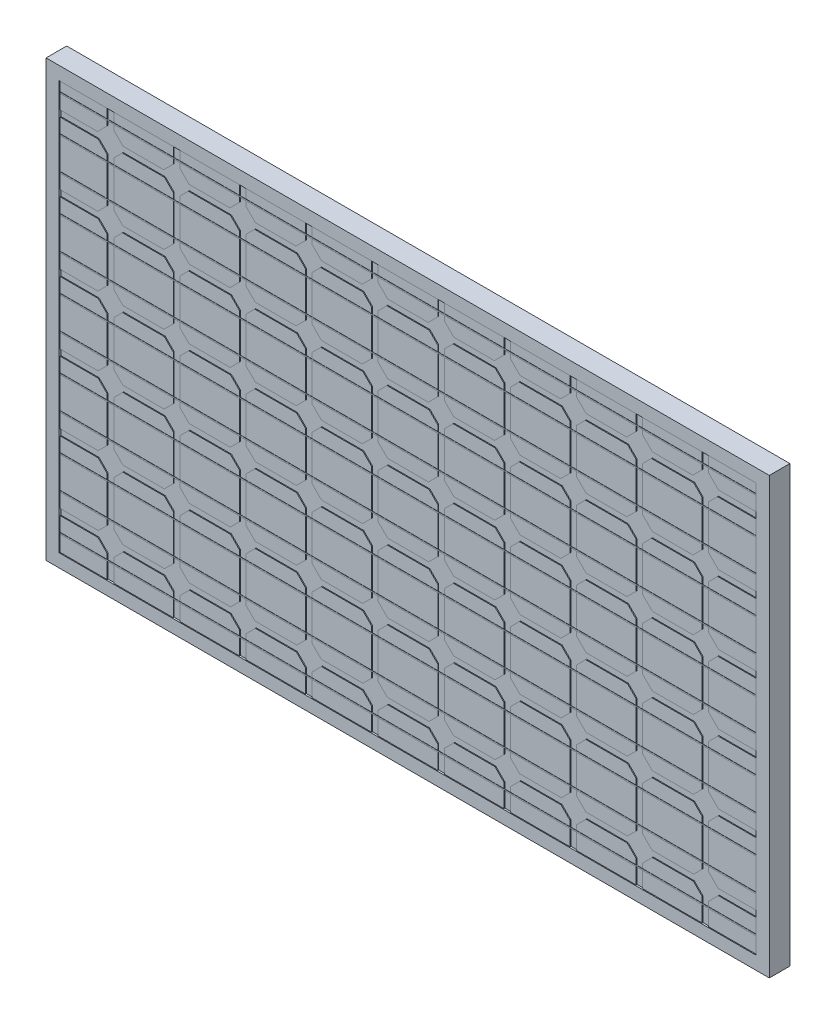
SolidWorks part; units mm, degrees
ref_plane "Plan de face" through (0, 0, 0) normal (0, 0, 1) x (1, 0, 0)
ref_plane "Plan de dessus" through (0, 0, 0) normal (0, 1, 0) x (1, 0, 0)
ref_plane "Plan de droite" through (0, 0, 0) normal (1, 0, 0) x (0, 0, -1)
sketch "Esquisse1" plane through (0, 0, 0) normal (0, 0, 1) x (1, 0, 0)
  line L0 (41, -41) -> (1609, -41)
  line L1 (0, 0) -> (1650, 0)
  line L2 (0, 0) -> (0, -993)
  line L3 (0, -993) -> (1650, -993)
  line L4 (1650, 0) -> (1650, -993)
  line L5 (1609, -41) -> (1609, -952)
  line L6 (41, -952) -> (1609, -952)
  line L7 (41, -41) -> (41, -952)
  dimension "D1" = 1650
  dimension "D2" = 993
  dimension "D3" = 41
extrude "Boss.-Extru.1" add sketch "Esquisse1" along normal blind 35
sketch "Esquisse2" plane through (0, 0, 35) normal (0, 0, 1) x (1, 0, 0)
  line L4 (0, 0) -> (0, -993)
  line L5 (0, -993) -> (1650, -993)
  line L6 (1650, -993) -> (1650, 0)
  line L7 (1650, 0) -> (0, 0)
  line L8 (0, 0) -> (0, -993)
  line L9 (0, -993) -> (1650, -993)
  line L10 (1650, -993) -> (1650, 0)
  line L11 (1650, 0) -> (0, 0)
  dimension "D1" = 0
extrude "Boss.-Extru.2" add sketch "Esquisse2" along normal blind 10
sketch "Esquisse3" plane through (0, 0, 45) normal (0, 0, 1) x (1, 0, 0)
  line L0 (1650, 0) -> (0, 0) construction
  line L1 (152.429, 0) -> (137.49, 0)
  line L2 (152.429, 0) -> (152.429, -993)
  line L3 (152.429, -993) -> (137.49, -993)
  line L4 (137.49, 0) -> (137.49, -993)
  line L5 (0, -993) -> (1650, -993) construction
  line L6 (303.2515, 0) -> (303.2515, -993)
  line L7 (303.2515, 0) -> (288.3124, 0)
  line L8 (288.3124, 0) -> (288.3124, -993)
  line L9 (303.2515, -993) -> (288.3124, -993)
  line L10 (454.0739, 0) -> (454.0739, -993)
  line L11 (454.0739, 0) -> (439.1349, 0)
  line L12 (439.1349, 0) -> (439.1349, -993)
  line L13 (454.0739, -993) -> (439.1349, -993)
  line L14 (604.8963, 0) -> (604.8963, -993)
  line L15 (604.8963, 0) -> (589.9573, 0)
  line L16 (589.9573, 0) -> (589.9573, -993)
  line L17 (604.8963, -993) -> (589.9573, -993)
  line L18 (755.7187, 0) -> (755.7187, -993)
  line L19 (755.7187, 0) -> (740.7797, 0)
  line L20 (740.7797, 0) -> (740.7797, -993)
  line L21 (755.7187, -993) -> (740.7797, -993)
  line L22 (906.5412, 0) -> (906.5412, -993)
  line L23 (906.5412, 0) -> (891.6021, 0)
  line L24 (891.6021, 0) -> (891.6021, -993)
  line L25 (906.5412, -993) -> (891.6021, -993)
  line L26 (1057.3636, 0) -> (1057.3636, -993)
  line L27 (1057.3636, 0) -> (1042.4246, 0)
  line L28 (1042.4246, 0) -> (1042.4246, -993)
  line L29 (1057.3636, -993) -> (1042.4246, -993)
  line L30 (1208.186, 0) -> (1208.186, -993)
  line L31 (1208.186, 0) -> (1193.247, 0)
  line L32 (1193.247, 0) -> (1193.247, -993)
  line L33 (1208.186, -993) -> (1193.247, -993)
  line L34 (1359.0084, 0) -> (1359.0084, -993)
  line L35 (1359.0084, 0) -> (1344.0694, 0)
  line L36 (1344.0694, 0) -> (1344.0694, -993)
  line L37 (1359.0084, -993) -> (1344.0694, -993)
  line L38 (1509.8309, 0) -> (1509.8309, -993)
  line L39 (1509.8309, 0) -> (1494.8918, 0)
  line L40 (1494.8918, 0) -> (1494.8918, -993)
  line L41 (1509.8309, -993) -> (1494.8918, -993)
  dimension "D1" = 10
extrude "Enlèv. mat.-Extru.1" cut sketch "Esquisse3" against normal blind 2
sketch "Esquisse4" plane through (0, 0, 45) normal (0, 0, 1) x (1, 0, 0)
  line L0 (0, 0) -> (0, -993) construction
  line L1 (0, -102.9559) -> (1650, -102.9559)
  line L2 (0, -102.9559) -> (0, -88.7684)
  line L3 (0, -88.7684) -> (1650, -88.7684)
  line L4 (1650, -102.9559) -> (1650, -88.7684)
  line L5 (1650, -993) -> (1650, 0) construction
  line L6 (0, -260.4453) -> (0, -246.2578)
  line L7 (0, -260.4453) -> (1650, -260.4453)
  line L8 (1650, -260.4453) -> (1650, -246.2578)
  line L9 (0, -246.2578) -> (1650, -246.2578)
  line L10 (0, -417.9348) -> (0, -403.7472)
  line L11 (0, -417.9348) -> (1650, -417.9348)
  line L12 (1650, -417.9348) -> (1650, -403.7472)
  line L13 (0, -403.7472) -> (1650, -403.7472)
  line L14 (0, -575.4242) -> (0, -561.2366)
  line L15 (0, -575.4242) -> (1650, -575.4242)
  line L16 (1650, -575.4242) -> (1650, -561.2366)
  line L17 (0, -561.2366) -> (1650, -561.2366)
  line L18 (0, -732.9136) -> (0, -718.7261)
  line L19 (0, -732.9136) -> (1650, -732.9136)
  line L20 (1650, -732.9136) -> (1650, -718.7261)
  line L21 (0, -718.7261) -> (1650, -718.7261)
  line L22 (0, -890.4031) -> (0, -876.2155)
  line L23 (0, -890.4031) -> (1650, -890.4031)
  line L24 (1650, -890.4031) -> (1650, -876.2155)
  line L25 (0, -876.2155) -> (1650, -876.2155)
  dimension "D1" = 6
extrude "Enlèv. mat.-Extru.2" cut sketch "Esquisse4" against normal blind 2
sketch "Esquisse5" plane through (0, 0, 45) normal (0, 0, 1) x (1, 0, 0)
  line L0 (30, -30) -> (30, -963)
  line L1 (0, 0) -> (1650, 0)
  line L2 (0, 0) -> (0, -993)
  line L3 (0, -993) -> (1650, -993)
  line L4 (1650, 0) -> (1650, -993)
  line L5 (30, -963) -> (1620, -963)
  line L6 (1620, -30) -> (1620, -963)
  line L7 (30, -30) -> (1620, -30)
  dimension "D1" = 30
extrude "Boss.-Extru.3" add sketch "Esquisse5" along normal blind 2 and the other way blind 2
sketch "Esquisse6" plane through (0, 0, 35) normal (0, 0, -1) x (-1, 0, 0)
  line L4 (-41, -952) -> (-41, -41)
  line L5 (-41, -41) -> (-1609, -41)
  line L6 (-1609, -41) -> (-1609, -952)
  line L7 (-1609, -952) -> (-41, -952)
  line L8 (-41, -952) -> (-41, -41)
  line L9 (-41, -41) -> (-1609, -41)
  line L10 (-1609, -41) -> (-1609, -952)
  line L11 (-1609, -952) -> (-41, -952)
  dimension "D1" = 0
extrude "Boss.-Extru.4" add sketch "Esquisse6" along normal up to surface (35 mm away) up to face at (825, -496.5, 0)
sketch "Esquisse7" plane through (0, 0, 43) normal (0, 0, 1) x (1, 0, 0)
  line L0 (152.429, -718.7261) -> (137.49, -732.9136) construction
  line L1 (137.49, -561.2366) -> (137.49, -732.9136) construction
  line L2 (152.429, -732.9136) -> (137.49, -718.7261) construction
  line L3 (144.9595, -761.1752) -> (180.3149, -725.8199)
  line L4 (144.9595, -761.1752) -> (109.6042, -725.8199)
  line L5 (180.3149, -725.8199) -> (144.9595, -690.4645)
  line L6 (109.6042, -725.8199) -> (144.9595, -690.4645)
  line L7 (144.9595, -761.1752) -> (144.9595, -690.4645) construction
  line L8 (180.3149, -725.8199) -> (109.6042, -725.8199) construction
  line L9 (137.49, -732.9136) -> (30, -732.9136) construction
  line L10 (137.49, -732.9136) -> (30, -732.9136) construction
  line L11 (295.8862, -761.1436) -> (331.2415, -725.7882)
  line L12 (295.8862, -761.1436) -> (260.5308, -725.7882)
  line L13 (331.2415, -725.7882) -> (295.8862, -690.4329)
  line L14 (260.5308, -725.7882) -> (295.8862, -690.4329)
  line L15 (303.3557, -718.6944) -> (288.4167, -732.882) construction
  line L16 (303.3557, -732.882) -> (288.4167, -718.6944) construction
  line L17 (295.8862, -761.1436) -> (295.8862, -690.4329) construction
  line L18 (331.2415, -725.7882) -> (260.5308, -725.7882) construction
  line L19 (446.8128, -761.1119) -> (482.1682, -725.7566)
  line L20 (446.8128, -761.1119) -> (411.4575, -725.7566)
  line L21 (482.1682, -725.7566) -> (446.8128, -690.4012)
  line L22 (411.4575, -725.7566) -> (446.8128, -690.4012)
  line L23 (454.2823, -718.6628) -> (439.3433, -732.8504) construction
  line L24 (454.2823, -732.8504) -> (439.3433, -718.6628) construction
  line L25 (446.8128, -761.1119) -> (446.8128, -690.4012) construction
  line L26 (482.1682, -725.7566) -> (411.4575, -725.7566) construction
  line L27 (597.7395, -761.0803) -> (633.0948, -725.7249)
  line L28 (597.7395, -761.0803) -> (562.3841, -725.7249)
  line L29 (633.0948, -725.7249) -> (597.7395, -690.3696)
  line L30 (562.3841, -725.7249) -> (597.7395, -690.3696)
  line L31 (605.209, -718.6312) -> (590.27, -732.8187) construction
  line L32 (605.209, -732.8187) -> (590.27, -718.6312) construction
  line L33 (597.7395, -761.0803) -> (597.7395, -690.3696) construction
  line L34 (633.0948, -725.7249) -> (562.3841, -725.7249) construction
  line L35 (748.6661, -761.0486) -> (784.0215, -725.6933)
  line L36 (748.6661, -761.0486) -> (713.3108, -725.6933)
  line L37 (784.0215, -725.6933) -> (748.6661, -690.3379)
  line L38 (713.3108, -725.6933) -> (748.6661, -690.3379)
  line L39 (756.1357, -718.5995) -> (741.1966, -732.7871) construction
  line L40 (756.1357, -732.7871) -> (741.1966, -718.5995) construction
  line L41 (748.6661, -761.0486) -> (748.6661, -690.3379) construction
  line L42 (784.0215, -725.6933) -> (713.3108, -725.6933) construction
  line L43 (899.5928, -761.017) -> (934.9481, -725.6616)
  line L44 (899.5928, -761.017) -> (864.2374, -725.6616)
  line L45 (934.9481, -725.6616) -> (899.5928, -690.3063)
  line L46 (864.2374, -725.6616) -> (899.5928, -690.3063)
  line L47 (907.0623, -718.5679) -> (892.1233, -732.7554) construction
  line L48 (907.0623, -732.7554) -> (892.1233, -718.5679) construction
  line L49 (899.5928, -761.017) -> (899.5928, -690.3063) construction
  line L50 (934.9481, -725.6616) -> (864.2374, -725.6616) construction
  line L51 (1050.5194, -760.9853) -> (1085.8748, -725.63)
  line L52 (1050.5194, -760.9853) -> (1015.1641, -725.63)
  line L53 (1085.8748, -725.63) -> (1050.5194, -690.2747)
  line L54 (1015.1641, -725.63) -> (1050.5194, -690.2747)
  line L55 (1057.989, -718.5362) -> (1043.0499, -732.7238) construction
  line L56 (1057.989, -732.7238) -> (1043.0499, -718.5362) construction
  line L57 (1050.5194, -760.9853) -> (1050.5194, -690.2747) construction
  line L58 (1085.8748, -725.63) -> (1015.1641, -725.63) construction
  line L59 (1201.4461, -760.9537) -> (1236.8014, -725.5984)
  line L60 (1201.4461, -760.9537) -> (1166.0908, -725.5984)
  line L61 (1236.8014, -725.5984) -> (1201.4461, -690.243)
  line L62 (1166.0908, -725.5984) -> (1201.4461, -690.243)
  line L63 (1208.9156, -718.5046) -> (1193.9766, -732.6921) construction
  line L64 (1208.9156, -732.6921) -> (1193.9766, -718.5046) construction
  line L65 (1201.4461, -760.9537) -> (1201.4461, -690.243) construction
  line L66 (1236.8014, -725.5984) -> (1166.0908, -725.5984) construction
  line L67 (1352.3727, -760.9221) -> (1387.7281, -725.5667)
  line L68 (1352.3727, -760.9221) -> (1317.0174, -725.5667)
  line L69 (1387.7281, -725.5667) -> (1352.3727, -690.2114)
  line L70 (1317.0174, -725.5667) -> (1352.3727, -690.2114)
  line L71 (1359.8423, -718.4729) -> (1344.9032, -732.6605) construction
  line L72 (1359.8423, -732.6605) -> (1344.9032, -718.4729) construction
  line L73 (1352.3727, -760.9221) -> (1352.3727, -690.2114) construction
  line L74 (1387.7281, -725.5667) -> (1317.0174, -725.5667) construction
  line L75 (1503.2994, -760.8904) -> (1538.6547, -725.5351)
  line L76 (1503.2994, -760.8904) -> (1467.9441, -725.5351)
  line L77 (1538.6547, -725.5351) -> (1503.2994, -690.1797)
  line L78 (1467.9441, -725.5351) -> (1503.2994, -690.1797)
  line L79 (1510.7689, -718.4413) -> (1495.8299, -732.6289) construction
  line L80 (1510.7689, -732.6289) -> (1495.8299, -718.4413) construction
  line L81 (1503.2994, -760.8904) -> (1503.2994, -690.1797) construction
  line L82 (1538.6547, -725.5351) -> (1467.9441, -725.5351) construction
  line L83 (144.8256, -603.4824) -> (180.1809, -568.1271)
  line L84 (144.8256, -603.4824) -> (109.4703, -568.1271)
  line L85 (180.1809, -568.1271) -> (144.8256, -532.7718)
  line L86 (109.4703, -568.1271) -> (144.8256, -532.7718)
  line L87 (295.7523, -603.4508) -> (331.1076, -568.0955)
  line L88 (295.7523, -603.4508) -> (260.3969, -568.0955)
  line L89 (331.1076, -568.0955) -> (295.7523, -532.7401)
  line L90 (260.3969, -568.0955) -> (295.7523, -532.7401)
  line L91 (446.6789, -603.4192) -> (482.0342, -568.0638)
  line L92 (446.6789, -603.4192) -> (411.3236, -568.0638)
  line L93 (482.0342, -568.0638) -> (446.6789, -532.7085)
  line L94 (411.3236, -568.0638) -> (446.6789, -532.7085)
  line L95 (597.6056, -603.3875) -> (632.9609, -568.0322)
  line L96 (597.6056, -603.3875) -> (562.2502, -568.0322)
  line L97 (632.9609, -568.0322) -> (597.6056, -532.6768)
  line L98 (562.2502, -568.0322) -> (597.6056, -532.6768)
  line L99 (748.5322, -603.3559) -> (783.8875, -568.0005)
  line L100 (748.5322, -603.3559) -> (713.1769, -568.0005)
  line L101 (783.8875, -568.0005) -> (748.5322, -532.6452)
  line L102 (713.1769, -568.0005) -> (748.5322, -532.6452)
  line L103 (899.4589, -603.3242) -> (934.8142, -567.9689)
  line L104 (899.4589, -603.3242) -> (864.1035, -567.9689)
  line L105 (934.8142, -567.9689) -> (899.4589, -532.6136)
  line L106 (864.1035, -567.9689) -> (899.4589, -532.6136)
  line L107 (1050.3855, -603.2926) -> (1085.7408, -567.9373)
  line L108 (1050.3855, -603.2926) -> (1015.0302, -567.9373)
  line L109 (1085.7408, -567.9373) -> (1050.3855, -532.5819)
  line L110 (1015.0302, -567.9373) -> (1050.3855, -532.5819)
  line L111 (1201.3122, -603.2609) -> (1236.6675, -567.9056)
  line L112 (1201.3122, -603.2609) -> (1165.9568, -567.9056)
  line L113 (1236.6675, -567.9056) -> (1201.3122, -532.5503)
  line L114 (1165.9568, -567.9056) -> (1201.3122, -532.5503)
  line L115 (1352.2388, -603.2293) -> (1387.5942, -567.874)
  line L116 (1352.2388, -603.2293) -> (1316.8835, -567.874)
  line L117 (1387.5942, -567.874) -> (1352.2388, -532.5186)
  line L118 (1316.8835, -567.874) -> (1352.2388, -532.5186)
  line L119 (1503.1655, -603.1977) -> (1538.5208, -567.8423)
  line L120 (1503.1655, -603.1977) -> (1467.8101, -567.8423)
  line L121 (1538.5208, -567.8423) -> (1503.1655, -532.487)
  line L122 (1467.8101, -567.8423) -> (1503.1655, -532.487)
  line L123 (152.2951, -561.0333) -> (137.3561, -575.2209) construction
  line L124 (152.2951, -575.2209) -> (137.3561, -561.0333) construction
  line L125 (144.8256, -603.4824) -> (144.8256, -532.7718) construction
  line L126 (180.1809, -568.1271) -> (109.4703, -568.1271) construction
  line L127 (303.2218, -561.0017) -> (288.2827, -575.1892) construction
  line L128 (303.2218, -575.1892) -> (288.2827, -561.0017) construction
  line L129 (295.7523, -603.4508) -> (295.7523, -532.7401) construction
  line L130 (331.1076, -568.0955) -> (260.3969, -568.0955) construction
  line L131 (454.1484, -560.97) -> (439.2094, -575.1576) construction
  line L132 (454.1484, -575.1576) -> (439.2094, -560.97) construction
  line L133 (446.6789, -603.4192) -> (446.6789, -532.7085) construction
  line L134 (482.0342, -568.0638) -> (411.3236, -568.0638) construction
  line L135 (605.0751, -560.9384) -> (590.136, -575.126) construction
  line L136 (605.0751, -575.126) -> (590.136, -560.9384) construction
  line L137 (597.6056, -603.3875) -> (597.6056, -532.6768) construction
  line L138 (632.9609, -568.0322) -> (562.2502, -568.0322) construction
  line L139 (756.0017, -560.9068) -> (741.0627, -575.0943) construction
  line L140 (756.0017, -575.0943) -> (741.0627, -560.9068) construction
  line L141 (748.5322, -603.3559) -> (748.5322, -532.6452) construction
  line L142 (783.8875, -568.0005) -> (713.1769, -568.0005) construction
  line L143 (906.9284, -560.8751) -> (891.9893, -575.0627) construction
  line L144 (906.9284, -575.0627) -> (891.9893, -560.8751) construction
  line L145 (899.4589, -603.3242) -> (899.4589, -532.6136) construction
  line L146 (934.8142, -567.9689) -> (864.1035, -567.9689) construction
  line L147 (1057.855, -560.8435) -> (1042.916, -575.031) construction
  line L148 (1057.855, -575.031) -> (1042.916, -560.8435) construction
  line L149 (1050.3855, -603.2926) -> (1050.3855, -532.5819) construction
  line L150 (1085.7408, -567.9373) -> (1015.0302, -567.9373) construction
  line L151 (1208.7817, -560.8118) -> (1193.8426, -574.9994) construction
  line L152 (1208.7817, -574.9994) -> (1193.8426, -560.8118) construction
  line L153 (1201.3122, -603.2609) -> (1201.3122, -532.5503) construction
  line L154 (1236.6675, -567.9056) -> (1165.9568, -567.9056) construction
  line L155 (1359.7083, -560.7802) -> (1344.7693, -574.9677) construction
  line L156 (1359.7083, -574.9677) -> (1344.7693, -560.7802) construction
  line L157 (1352.2388, -603.2293) -> (1352.2388, -532.5186) construction
  line L158 (1387.5942, -567.874) -> (1316.8835, -567.874) construction
  line L159 (1510.635, -560.7485) -> (1495.6959, -574.9361) construction
  line L160 (1510.635, -574.9361) -> (1495.6959, -560.7485) construction
  line L161 (1503.1655, -603.1977) -> (1503.1655, -532.487) construction
  line L162 (1538.5208, -567.8423) -> (1467.8101, -567.8423) construction
  line L163 (144.6917, -445.7897) -> (180.047, -410.4344)
  line L164 (144.6917, -445.7897) -> (109.3363, -410.4344)
  line L165 (180.047, -410.4344) -> (144.6917, -375.079)
  line L166 (109.3363, -410.4344) -> (144.6917, -375.079)
  line L167 (295.6183, -445.7581) -> (330.9737, -410.4027)
  line L168 (295.6183, -445.7581) -> (260.263, -410.4027)
  line L169 (330.9737, -410.4027) -> (295.6183, -375.0474)
  line L170 (260.263, -410.4027) -> (295.6183, -375.0474)
  line L171 (446.545, -445.7264) -> (481.9003, -410.3711)
  line L172 (446.545, -445.7264) -> (411.1896, -410.3711)
  line L173 (481.9003, -410.3711) -> (446.545, -375.0157)
  line L174 (411.1896, -410.3711) -> (446.545, -375.0157)
  line L175 (597.4716, -445.6948) -> (632.827, -410.3394)
  line L176 (597.4716, -445.6948) -> (562.1163, -410.3394)
  line L177 (632.827, -410.3394) -> (597.4716, -374.9841)
  line L178 (562.1163, -410.3394) -> (597.4716, -374.9841)
  line L179 (748.3983, -445.6631) -> (783.7536, -410.3078)
  line L180 (748.3983, -445.6631) -> (713.0429, -410.3078)
  line L181 (783.7536, -410.3078) -> (748.3983, -374.9524)
  line L182 (713.0429, -410.3078) -> (748.3983, -374.9524)
  line L183 (899.3249, -445.6315) -> (934.6803, -410.2761)
  line L184 (899.3249, -445.6315) -> (863.9696, -410.2761)
  line L185 (934.6803, -410.2761) -> (899.3249, -374.9208)
  line L186 (863.9696, -410.2761) -> (899.3249, -374.9208)
  line L187 (1050.2516, -445.5998) -> (1085.6069, -410.2445)
  line L188 (1050.2516, -445.5998) -> (1014.8962, -410.2445)
  line L189 (1085.6069, -410.2445) -> (1050.2516, -374.8892)
  line L190 (1014.8962, -410.2445) -> (1050.2516, -374.8892)
  line L191 (1201.1782, -445.5682) -> (1236.5336, -410.2129)
  line L192 (1201.1782, -445.5682) -> (1165.8229, -410.2129)
  line L193 (1236.5336, -410.2129) -> (1201.1782, -374.8575)
  line L194 (1165.8229, -410.2129) -> (1201.1782, -374.8575)
  line L195 (1352.1049, -445.5366) -> (1387.4602, -410.1812)
  line L196 (1352.1049, -445.5366) -> (1316.7495, -410.1812)
  line L197 (1387.4602, -410.1812) -> (1352.1049, -374.8259)
  line L198 (1316.7495, -410.1812) -> (1352.1049, -374.8259)
  line L199 (1503.0315, -445.5049) -> (1538.3869, -410.1496)
  line L200 (1503.0315, -445.5049) -> (1467.6762, -410.1496)
  line L201 (1538.3869, -410.1496) -> (1503.0315, -374.7942)
  line L202 (1467.6762, -410.1496) -> (1503.0315, -374.7942)
  line L203 (152.1612, -403.3406) -> (137.2222, -417.5281) construction
  line L204 (152.1612, -417.5281) -> (137.2222, -403.3406) construction
  line L205 (144.6917, -445.7897) -> (144.6917, -375.079) construction
  line L206 (180.047, -410.4344) -> (109.3363, -410.4344) construction
  line L207 (303.0878, -403.3089) -> (288.1488, -417.4965) construction
  line L208 (303.0878, -417.4965) -> (288.1488, -403.3089) construction
  line L209 (295.6183, -445.7581) -> (295.6183, -375.0474) construction
  line L210 (330.9737, -410.4027) -> (260.263, -410.4027) construction
  line L211 (454.0145, -403.2773) -> (439.0755, -417.4649) construction
  line L212 (454.0145, -417.4649) -> (439.0755, -403.2773) construction
  line L213 (446.545, -445.7264) -> (446.545, -375.0157) construction
  line L214 (481.9003, -410.3711) -> (411.1896, -410.3711) construction
  line L215 (604.9411, -403.2457) -> (590.0021, -417.4332) construction
  line L216 (604.9411, -417.4332) -> (590.0021, -403.2457) construction
  line L217 (597.4716, -445.6948) -> (597.4716, -374.9841) construction
  line L218 (632.827, -410.3394) -> (562.1163, -410.3394) construction
  line L219 (755.8678, -403.214) -> (740.9288, -417.4016) construction
  line L220 (755.8678, -417.4016) -> (740.9288, -403.214) construction
  line L221 (748.3983, -445.6631) -> (748.3983, -374.9524) construction
  line L222 (783.7536, -410.3078) -> (713.0429, -410.3078) construction
  line L223 (906.7944, -403.1824) -> (891.8554, -417.3699) construction
  line L224 (906.7944, -417.3699) -> (891.8554, -403.1824) construction
  line L225 (899.3249, -445.6315) -> (899.3249, -374.9208) construction
  line L226 (934.6803, -410.2761) -> (863.9696, -410.2761) construction
  line L227 (1057.7211, -403.1507) -> (1042.7821, -417.3383) construction
  line L228 (1057.7211, -417.3383) -> (1042.7821, -403.1507) construction
  line L229 (1050.2516, -445.5998) -> (1050.2516, -374.8892) construction
  line L230 (1085.6069, -410.2445) -> (1014.8962, -410.2445) construction
  line L231 (1208.6477, -403.1191) -> (1193.7087, -417.3066) construction
  line L232 (1208.6477, -417.3066) -> (1193.7087, -403.1191) construction
  line L233 (1201.1782, -445.5682) -> (1201.1782, -374.8575) construction
  line L234 (1236.5336, -410.2129) -> (1165.8229, -410.2129) construction
  line L235 (1359.5744, -403.0874) -> (1344.6354, -417.275) construction
  line L236 (1359.5744, -417.275) -> (1344.6354, -403.0874) construction
  line L237 (1352.1049, -445.5366) -> (1352.1049, -374.8259) construction
  line L238 (1387.4602, -410.1812) -> (1316.7495, -410.1812) construction
  line L239 (1510.5011, -403.0558) -> (1495.562, -417.2434) construction
  line L240 (1510.5011, -417.2434) -> (1495.562, -403.0558) construction
  line L241 (1503.0315, -445.5049) -> (1503.0315, -374.7942) construction
  line L242 (1538.3869, -410.1496) -> (1467.6762, -410.1496) construction
  line L243 (144.5577, -288.0969) -> (179.9131, -252.7416)
  line L244 (144.5577, -288.0969) -> (109.2024, -252.7416)
  line L245 (179.9131, -252.7416) -> (144.5577, -217.3863)
  line L246 (109.2024, -252.7416) -> (144.5577, -217.3863)
  line L247 (295.4844, -288.0653) -> (330.8397, -252.71)
  line L248 (295.4844, -288.0653) -> (260.1291, -252.71)
  line L249 (330.8397, -252.71) -> (295.4844, -217.3546)
  line L250 (260.1291, -252.71) -> (295.4844, -217.3546)
  line L251 (446.411, -288.0337) -> (481.7664, -252.6783)
  line L252 (446.411, -288.0337) -> (411.0557, -252.6783)
  line L253 (481.7664, -252.6783) -> (446.411, -217.323)
  line L254 (411.0557, -252.6783) -> (446.411, -217.323)
  line L255 (597.3377, -288.002) -> (632.693, -252.6467)
  line L256 (597.3377, -288.002) -> (561.9824, -252.6467)
  line L257 (632.693, -252.6467) -> (597.3377, -217.2913)
  line L258 (561.9824, -252.6467) -> (597.3377, -217.2913)
  line L259 (748.2643, -287.9704) -> (783.6197, -252.615)
  line L260 (748.2643, -287.9704) -> (712.909, -252.615)
  line L261 (783.6197, -252.615) -> (748.2643, -217.2597)
  line L262 (712.909, -252.615) -> (748.2643, -217.2597)
  line L263 (899.191, -287.9387) -> (934.5463, -252.5834)
  line L264 (899.191, -287.9387) -> (863.8357, -252.5834)
  line L265 (934.5463, -252.5834) -> (899.191, -217.2281)
  line L266 (863.8357, -252.5834) -> (899.191, -217.2281)
  line L267 (1050.1177, -287.9071) -> (1085.473, -252.5518)
  line L268 (1050.1177, -287.9071) -> (1014.7623, -252.5518)
  line L269 (1085.473, -252.5518) -> (1050.1177, -217.1964)
  line L270 (1014.7623, -252.5518) -> (1050.1177, -217.1964)
  line L271 (1201.0443, -287.8754) -> (1236.3996, -252.5201)
  line L272 (1201.0443, -287.8754) -> (1165.689, -252.5201)
  line L273 (1236.3996, -252.5201) -> (1201.0443, -217.1648)
  line L274 (1165.689, -252.5201) -> (1201.0443, -217.1648)
  line L275 (1351.971, -287.8438) -> (1387.3263, -252.4885)
  line L276 (1351.971, -287.8438) -> (1316.6156, -252.4885)
  line L277 (1387.3263, -252.4885) -> (1351.971, -217.1331)
  line L278 (1316.6156, -252.4885) -> (1351.971, -217.1331)
  line L279 (1502.8976, -287.8122) -> (1538.2529, -252.4568)
  line L280 (1502.8976, -287.8122) -> (1467.5423, -252.4568)
  line L281 (1538.2529, -252.4568) -> (1502.8976, -217.1015)
  line L282 (1467.5423, -252.4568) -> (1502.8976, -217.1015)
  line L283 (152.0273, -245.6478) -> (137.0882, -259.8354) construction
  line L284 (152.0273, -259.8354) -> (137.0882, -245.6478) construction
  line L285 (144.5577, -288.0969) -> (144.5577, -217.3863) construction
  line L286 (179.9131, -252.7416) -> (109.2024, -252.7416) construction
  line L287 (302.9539, -245.6162) -> (288.0149, -259.8037) construction
  line L288 (302.9539, -259.8037) -> (288.0149, -245.6162) construction
  line L289 (295.4844, -288.0653) -> (295.4844, -217.3546) construction
  line L290 (330.8397, -252.71) -> (260.1291, -252.71) construction
  line L291 (453.8806, -245.5845) -> (438.9415, -259.7721) construction
  line L292 (453.8806, -259.7721) -> (438.9415, -245.5845) construction
  line L293 (446.411, -288.0337) -> (446.411, -217.323) construction
  line L294 (481.7664, -252.6783) -> (411.0557, -252.6783) construction
  line L295 (604.8072, -245.5529) -> (589.8682, -259.7405) construction
  line L296 (604.8072, -259.7405) -> (589.8682, -245.5529) construction
  line L297 (597.3377, -288.002) -> (597.3377, -217.2913) construction
  line L298 (632.693, -252.6467) -> (561.9824, -252.6467) construction
  line L299 (755.7339, -245.5213) -> (740.7948, -259.7088) construction
  line L300 (755.7339, -259.7088) -> (740.7948, -245.5213) construction
  line L301 (748.2643, -287.9704) -> (748.2643, -217.2597) construction
  line L302 (783.6197, -252.615) -> (712.909, -252.615) construction
  line L303 (906.6605, -245.4896) -> (891.7215, -259.6772) construction
  line L304 (906.6605, -259.6772) -> (891.7215, -245.4896) construction
  line L305 (899.191, -287.9387) -> (899.191, -217.2281) construction
  line L306 (934.5463, -252.5834) -> (863.8357, -252.5834) construction
  line L307 (1057.5872, -245.458) -> (1042.6481, -259.6455) construction
  line L308 (1057.5872, -259.6455) -> (1042.6481, -245.458) construction
  line L309 (1050.1177, -287.9071) -> (1050.1177, -217.1964) construction
  line L310 (1085.473, -252.5518) -> (1014.7623, -252.5518) construction
  line L311 (1208.5138, -245.4263) -> (1193.5748, -259.6139) construction
  line L312 (1208.5138, -259.6139) -> (1193.5748, -245.4263) construction
  line L313 (1201.0443, -287.8754) -> (1201.0443, -217.1648) construction
  line L314 (1236.3996, -252.5201) -> (1165.689, -252.5201) construction
  line L315 (1359.4405, -245.3947) -> (1344.5014, -259.5822) construction
  line L316 (1359.4405, -259.5822) -> (1344.5014, -245.3947) construction
  line L317 (1351.971, -287.8438) -> (1351.971, -217.1331) construction
  line L318 (1387.3263, -252.4885) -> (1316.6156, -252.4885) construction
  line L319 (1510.3671, -245.363) -> (1495.4281, -259.5506) construction
  line L320 (1510.3671, -259.5506) -> (1495.4281, -245.363) construction
  line L321 (1502.8976, -287.8122) -> (1502.8976, -217.1015) construction
  line L322 (1538.2529, -252.4568) -> (1467.5423, -252.4568) construction
  line L323 (144.4238, -130.4042) -> (179.7791, -95.0489)
  line L324 (144.4238, -130.4042) -> (109.0685, -95.0489)
  line L325 (179.7791, -95.0489) -> (144.4238, -59.6935)
  line L326 (109.0685, -95.0489) -> (144.4238, -59.6935)
  line L327 (295.3505, -130.3726) -> (330.7058, -95.0172)
  line L328 (295.3505, -130.3726) -> (259.9951, -95.0172)
  line L329 (330.7058, -95.0172) -> (295.3505, -59.6619)
  line L330 (259.9951, -95.0172) -> (295.3505, -59.6619)
  line L331 (446.2771, -130.3409) -> (481.6325, -94.9856)
  line L332 (446.2771, -130.3409) -> (410.9218, -94.9856)
  line L333 (481.6325, -94.9856) -> (446.2771, -59.6302)
  line L334 (410.9218, -94.9856) -> (446.2771, -59.6302)
  line L335 (597.2038, -130.3093) -> (632.5591, -94.9539)
  line L336 (597.2038, -130.3093) -> (561.8484, -94.9539)
  line L337 (632.5591, -94.9539) -> (597.2038, -59.5986)
  line L338 (561.8484, -94.9539) -> (597.2038, -59.5986)
  line L339 (748.1304, -130.2776) -> (783.4858, -94.9223)
  line L340 (748.1304, -130.2776) -> (712.7751, -94.9223)
  line L341 (783.4858, -94.9223) -> (748.1304, -59.5669)
  line L342 (712.7751, -94.9223) -> (748.1304, -59.5669)
  line L343 (899.0571, -130.246) -> (934.4124, -94.8906)
  line L344 (899.0571, -130.246) -> (863.7017, -94.8906)
  line L345 (934.4124, -94.8906) -> (899.0571, -59.5353)
  line L346 (863.7017, -94.8906) -> (899.0571, -59.5353)
  line L347 (1049.9837, -130.2143) -> (1085.3391, -94.859)
  line L348 (1049.9837, -130.2143) -> (1014.6284, -94.859)
  line L349 (1085.3391, -94.859) -> (1049.9837, -59.5037)
  line L350 (1014.6284, -94.859) -> (1049.9837, -59.5037)
  line L351 (1200.9104, -130.1827) -> (1236.2657, -94.8274)
  line L352 (1200.9104, -130.1827) -> (1165.555, -94.8274)
  line L353 (1236.2657, -94.8274) -> (1200.9104, -59.472)
  line L354 (1165.555, -94.8274) -> (1200.9104, -59.472)
  line L355 (1351.837, -130.1511) -> (1387.1924, -94.7957)
  line L356 (1351.837, -130.1511) -> (1316.4817, -94.7957)
  line L357 (1387.1924, -94.7957) -> (1351.837, -59.4404)
  line L358 (1316.4817, -94.7957) -> (1351.837, -59.4404)
  line L359 (1502.7637, -130.1194) -> (1538.119, -94.7641)
  line L360 (1502.7637, -130.1194) -> (1467.4083, -94.7641)
  line L361 (1538.119, -94.7641) -> (1502.7637, -59.4087)
  line L362 (1467.4083, -94.7641) -> (1502.7637, -59.4087)
  line L363 (151.8933, -87.9551) -> (136.9543, -102.1426) construction
  line L364 (151.8933, -102.1426) -> (136.9543, -87.9551) construction
  line L365 (144.4238, -130.4042) -> (144.4238, -59.6935) construction
  line L366 (179.7791, -95.0489) -> (109.0685, -95.0489) construction
  line L367 (302.82, -87.9234) -> (287.8809, -102.111) construction
  line L368 (302.82, -102.111) -> (287.8809, -87.9234) construction
  line L369 (295.3505, -130.3726) -> (295.3505, -59.6619) construction
  line L370 (330.7058, -95.0172) -> (259.9951, -95.0172) construction
  line L371 (453.7466, -87.8918) -> (438.8076, -102.0794) construction
  line L372 (453.7466, -102.0794) -> (438.8076, -87.8918) construction
  line L373 (446.2771, -130.3409) -> (446.2771, -59.6302) construction
  line L374 (481.6325, -94.9856) -> (410.9218, -94.9856) construction
  line L375 (604.6733, -87.8601) -> (589.7343, -102.0477) construction
  line L376 (604.6733, -102.0477) -> (589.7343, -87.8601) construction
  line L377 (597.2038, -130.3093) -> (597.2038, -59.5986) construction
  line L378 (632.5591, -94.9539) -> (561.8484, -94.9539) construction
  line L379 (755.5999, -87.8285) -> (740.6609, -102.0161) construction
  line L380 (755.5999, -102.0161) -> (740.6609, -87.8285) construction
  line L381 (748.1304, -130.2776) -> (748.1304, -59.5669) construction
  line L382 (783.4858, -94.9223) -> (712.7751, -94.9223) construction
  line L383 (906.5266, -87.7969) -> (891.5876, -101.9844) construction
  line L384 (906.5266, -101.9844) -> (891.5876, -87.7969) construction
  line L385 (899.0571, -130.246) -> (899.0571, -59.5353) construction
  line L386 (934.4124, -94.8906) -> (863.7017, -94.8906) construction
  line L387 (1057.4532, -87.7652) -> (1042.5142, -101.9528) construction
  line L388 (1057.4532, -101.9528) -> (1042.5142, -87.7652) construction
  line L389 (1049.9837, -130.2143) -> (1049.9837, -59.5037) construction
  line L390 (1085.3391, -94.859) -> (1014.6284, -94.859) construction
  line L391 (1208.3799, -87.7336) -> (1193.4409, -101.9211) construction
  line L392 (1208.3799, -101.9211) -> (1193.4409, -87.7336) construction
  line L393 (1200.9104, -130.1827) -> (1200.9104, -59.472) construction
  line L394 (1236.2657, -94.8274) -> (1165.555, -94.8274) construction
  line L395 (1359.3065, -87.7019) -> (1344.3675, -101.8895) construction
  line L396 (1359.3065, -101.8895) -> (1344.3675, -87.7019) construction
  line L397 (1351.837, -130.1511) -> (1351.837, -59.4404) construction
  line L398 (1387.1924, -94.7957) -> (1316.4817, -94.7957) construction
  line L399 (1510.2332, -87.6703) -> (1495.2942, -101.8579) construction
  line L400 (1510.2332, -101.8579) -> (1495.2942, -87.6703) construction
  line L401 (1502.7637, -130.1194) -> (1502.7637, -59.4087) construction
  line L402 (1538.119, -94.7641) -> (1467.4083, -94.7641) construction
  line L403 (144.9595, -919.1752) -> (180.3149, -883.8199)
  line L404 (144.9595, -919.1752) -> (109.6042, -883.8199)
  line L405 (180.3149, -883.8199) -> (144.9595, -848.4645)
  line L406 (109.6042, -883.8199) -> (144.9595, -848.4645)
  line L407 (295.8862, -919.1436) -> (331.2415, -883.7882)
  line L408 (295.8862, -919.1436) -> (260.5308, -883.7882)
  line L409 (331.2415, -883.7882) -> (295.8862, -848.4329)
  line L410 (260.5308, -883.7882) -> (295.8862, -848.4329)
  line L411 (446.8128, -919.1119) -> (482.1682, -883.7566)
  line L412 (446.8128, -919.1119) -> (411.4575, -883.7566)
  line L413 (482.1682, -883.7566) -> (446.8128, -848.4012)
  line L414 (411.4575, -883.7566) -> (446.8128, -848.4012)
  line L415 (597.7395, -919.0803) -> (633.0948, -883.7249)
  line L416 (597.7395, -919.0803) -> (562.3841, -883.7249)
  line L417 (633.0948, -883.7249) -> (597.7395, -848.3696)
  line L418 (562.3841, -883.7249) -> (597.7395, -848.3696)
  line L419 (748.6661, -919.0486) -> (784.0215, -883.6933)
  line L420 (748.6661, -919.0486) -> (713.3108, -883.6933)
  line L421 (784.0215, -883.6933) -> (748.6661, -848.3379)
  line L422 (713.3108, -883.6933) -> (748.6661, -848.3379)
  line L423 (899.5928, -919.017) -> (934.9481, -883.6616)
  line L424 (899.5928, -919.017) -> (864.2374, -883.6616)
  line L425 (934.9481, -883.6616) -> (899.5928, -848.3063)
  line L426 (864.2374, -883.6616) -> (899.5928, -848.3063)
  line L427 (1050.5194, -918.9853) -> (1085.8748, -883.63)
  line L428 (1050.5194, -918.9853) -> (1015.1641, -883.63)
  line L429 (1085.8748, -883.63) -> (1050.5194, -848.2747)
  line L430 (1015.1641, -883.63) -> (1050.5194, -848.2747)
  line L431 (1201.4461, -918.9537) -> (1236.8014, -883.5984)
  line L432 (1201.4461, -918.9537) -> (1166.0908, -883.5984)
  line L433 (1236.8014, -883.5984) -> (1201.4461, -848.243)
  line L434 (1166.0908, -883.5984) -> (1201.4461, -848.243)
  line L435 (1352.3727, -918.9221) -> (1387.7281, -883.5667)
  line L436 (1352.3727, -918.9221) -> (1317.0174, -883.5667)
  line L437 (1387.7281, -883.5667) -> (1352.3727, -848.2114)
  line L438 (1317.0174, -883.5667) -> (1352.3727, -848.2114)
  line L439 (1503.2994, -918.8904) -> (1538.6547, -883.5351)
  line L440 (1503.2994, -918.8904) -> (1467.9441, -883.5351)
  line L441 (1538.6547, -883.5351) -> (1503.2994, -848.1797)
  line L442 (1467.9441, -883.5351) -> (1503.2994, -848.1797)
  line L443 (152.429, -876.7261) -> (137.49, -890.9136) construction
  line L444 (152.429, -890.9136) -> (137.49, -876.7261) construction
  line L445 (144.9595, -919.1752) -> (144.9595, -848.4645) construction
  line L446 (180.3149, -883.8199) -> (109.6042, -883.8199) construction
  line L447 (303.3557, -876.6944) -> (288.4167, -890.882) construction
  line L448 (303.3557, -890.882) -> (288.4167, -876.6944) construction
  line L449 (295.8862, -919.1436) -> (295.8862, -848.4329) construction
  line L450 (331.2415, -883.7882) -> (260.5308, -883.7882) construction
  line L451 (454.2823, -876.6628) -> (439.3433, -890.8504) construction
  line L452 (454.2823, -890.8504) -> (439.3433, -876.6628) construction
  line L453 (446.8128, -919.1119) -> (446.8128, -848.4012) construction
  line L454 (482.1682, -883.7566) -> (411.4575, -883.7566) construction
  line L455 (605.209, -876.6312) -> (590.27, -890.8187) construction
  line L456 (605.209, -890.8187) -> (590.27, -876.6312) construction
  line L457 (597.7395, -919.0803) -> (597.7395, -848.3696) construction
  line L458 (633.0948, -883.7249) -> (562.3841, -883.7249) construction
  line L459 (756.1357, -876.5995) -> (741.1966, -890.7871) construction
  line L460 (756.1357, -890.7871) -> (741.1966, -876.5995) construction
  line L461 (748.6661, -919.0486) -> (748.6661, -848.3379) construction
  line L462 (784.0215, -883.6933) -> (713.3108, -883.6933) construction
  line L463 (907.0623, -876.5679) -> (892.1233, -890.7554) construction
  line L464 (907.0623, -890.7554) -> (892.1233, -876.5679) construction
  line L465 (899.5928, -919.017) -> (899.5928, -848.3063) construction
  line L466 (934.9481, -883.6616) -> (864.2374, -883.6616) construction
  line L467 (1057.989, -876.5362) -> (1043.0499, -890.7238) construction
  line L468 (1057.989, -890.7238) -> (1043.0499, -876.5362) construction
  line L469 (1050.5194, -918.9853) -> (1050.5194, -848.2747) construction
  line L470 (1085.8748, -883.63) -> (1015.1641, -883.63) construction
  line L471 (1208.9156, -876.5046) -> (1193.9766, -890.6921) construction
  line L472 (1208.9156, -890.6921) -> (1193.9766, -876.5046) construction
  line L473 (1201.4461, -918.9537) -> (1201.4461, -848.243) construction
  line L474 (1236.8014, -883.5984) -> (1166.0908, -883.5984) construction
  line L475 (1359.8423, -876.4729) -> (1344.9032, -890.6605) construction
  line L476 (1359.8423, -890.6605) -> (1344.9032, -876.4729) construction
  line L477 (1352.3727, -918.9221) -> (1352.3727, -848.2114) construction
  line L478 (1387.7281, -883.5667) -> (1317.0174, -883.5667) construction
  line L479 (1510.7689, -876.4413) -> (1495.8299, -890.6289) construction
  line L480 (1510.7689, -890.6289) -> (1495.8299, -876.4413) construction
  line L481 (1503.2994, -918.8904) -> (1503.2994, -848.1797) construction
  line L482 (1538.6547, -883.5351) -> (1467.9441, -883.5351) construction
  line L483 (1503.2994, -725.5351) -> (1503.2994, -883.5351) construction
  line L484 (0, -993) -> (1650, -993) construction
  line L485 (1650, -993) -> (1650, 0) construction
  point P10 (144.9595, -725.8199)
  point P23 (295.8862, -725.7882)
  point P32 (446.8128, -725.7566)
  point P41 (597.7395, -725.7249)
  point P50 (748.6661, -725.6933)
  point P59 (899.5928, -725.6616)
  point P68 (1050.5194, -725.63)
  point P77 (1201.4461, -725.5984)
  point P86 (1352.3727, -725.5667)
  point P95 (1503.2994, -725.5351)
  point P104 (144.8256, -568.1271)
  point P113 (295.7523, -568.0955)
  point P122 (446.6789, -568.0638)
  point P131 (597.6056, -568.0322)
  point P140 (748.5322, -568.0005)
  point P149 (899.4589, -567.9689)
  point P158 (1050.3855, -567.9373)
  point P167 (1201.3122, -567.9056)
  point P176 (1352.2388, -567.874)
  point P185 (1503.1655, -567.8423)
  point P194 (144.6917, -410.4344)
  point P203 (295.6183, -410.4027)
  point P212 (446.545, -410.3711)
  point P221 (597.4716, -410.3394)
  point P230 (748.3983, -410.3078)
  point P239 (899.3249, -410.2761)
  point P248 (1050.2516, -410.2445)
  point P257 (1201.1782, -410.2129)
  point P266 (1352.1049, -410.1812)
  point P275 (1503.0315, -410.1496)
  point P284 (144.5577, -252.7416)
  point P293 (295.4844, -252.71)
  point P302 (446.411, -252.6783)
  point P311 (597.3377, -252.6467)
  point P320 (748.2643, -252.615)
  point P329 (899.191, -252.5834)
  point P338 (1050.1177, -252.5518)
  point P347 (1201.0443, -252.5201)
  point P356 (1351.971, -252.4885)
  point P365 (1502.8976, -252.4568)
  point P374 (144.4238, -95.0489)
  point P383 (295.3505, -95.0172)
  point P392 (446.2771, -94.9856)
  point P401 (597.2038, -94.9539)
  point P410 (748.1304, -94.9223)
  point P419 (899.0571, -94.8906)
  point P428 (1049.9837, -94.859)
  point P437 (1200.9104, -94.8274)
  point P446 (1351.837, -94.7957)
  point P455 (1502.7637, -94.7641)
  point P465 (144.9595, -883.8199)
  point P474 (295.8862, -883.7882)
  point P483 (446.8128, -883.7566)
  point P492 (597.7395, -883.7249)
  point P501 (748.6661, -883.6933)
  point P510 (899.5928, -883.6616)
  point P519 (1050.5194, -883.63)
  point P528 (1201.4461, -883.5984)
  point P537 (1352.3727, -883.5667)
  point P546 (1503.2994, -883.5351)
  dimension "D1" = 10
  dimension "D2" = 5
  dimension "D4" = 109.4649
  dimension "D5" = 146.7006
  dimension "D6" = 50
  dimension "D3" = 2
extrude "Enlèv. mat.-Extru.3" cut sketch "Esquisse7" along normal blind 11
sketch "Esquisse8" plane through (0, 0, 45) normal (0, 0, 1) x (1, 0, 0)
  line L0 (30, -883.3093) -> (147.2694, -883.3093) construction
  line L1 (30, -876.2155) -> (30, -890.4031) construction
  line L2 (30, -890.4031) -> (30, -963) construction
  line L3 (30, -926.3093) -> (1620, -926.3093)
  line L4 (30, -926.3093) -> (30, -923.3093)
  line L5 (30, -923.3093) -> (1620, -923.3093)
  line L6 (1620, -926.3093) -> (1620, -923.3093)
  line L7 (1620, -963) -> (1620, -890.4031) construction
  line L8 (1620, -840.3093) -> (1620, -843.3093)
  line L9 (30, -843.3093) -> (1620, -843.3093)
  line L10 (30, -840.3093) -> (30, -843.3093)
  line L11 (30, -840.3093) -> (1620, -840.3093)
  line L12 (30, -768.8093) -> (1620, -768.8093)
  line L13 (30, -768.8093) -> (30, -765.8093)
  line L14 (30, -765.8093) -> (1620, -765.8093)
  line L15 (1620, -768.8093) -> (1620, -765.8093)
  line L16 (1620, -682.8093) -> (1620, -685.8093)
  line L17 (30, -685.8093) -> (1620, -685.8093)
  line L18 (30, -682.8093) -> (30, -685.8093)
  line L19 (30, -682.8093) -> (1620, -682.8093)
  line L20 (30, -725.8093) -> (147.2694, -725.8093) construction
  line L21 (30, -611.3093) -> (1620, -611.3093)
  line L22 (30, -611.3093) -> (30, -608.3093)
  line L23 (30, -608.3093) -> (1620, -608.3093)
  line L24 (1620, -611.3093) -> (1620, -608.3093)
  line L25 (1620, -525.3093) -> (1620, -528.3093)
  line L26 (30, -528.3093) -> (1620, -528.3093)
  line L27 (30, -525.3093) -> (30, -528.3093)
  line L28 (30, -525.3093) -> (1620, -525.3093)
  line L29 (30, -568.3093) -> (147.2694, -568.3093) construction
  line L30 (30, -453.8093) -> (1620, -453.8093)
  line L31 (30, -453.8093) -> (30, -450.8093)
  line L32 (30, -450.8093) -> (1620, -450.8093)
  line L33 (1620, -453.8093) -> (1620, -450.8093)
  line L34 (1620, -367.8093) -> (1620, -370.8093)
  line L35 (30, -370.8093) -> (1620, -370.8093)
  line L36 (30, -367.8093) -> (30, -370.8093)
  line L37 (30, -367.8093) -> (1620, -367.8093)
  line L38 (30, -410.8093) -> (147.2694, -410.8093) construction
  line L39 (30, -296.3093) -> (1620, -296.3093)
  line L40 (30, -296.3093) -> (30, -293.3093)
  line L41 (30, -293.3093) -> (1620, -293.3093)
  line L42 (1620, -296.3093) -> (1620, -293.3093)
  line L43 (1620, -210.3093) -> (1620, -213.3093)
  line L44 (30, -213.3093) -> (1620, -213.3093)
  line L45 (30, -210.3093) -> (30, -213.3093)
  line L46 (30, -210.3093) -> (1620, -210.3093)
  line L47 (30, -253.3093) -> (147.2694, -253.3093) construction
  line L48 (30, -138.8093) -> (1620, -138.8093)
  line L49 (30, -138.8093) -> (30, -135.8093)
  line L50 (30, -135.8093) -> (1620, -135.8093)
  line L51 (1620, -138.8093) -> (1620, -135.8093)
  line L52 (1620, -52.8093) -> (1620, -55.8093)
  line L53 (30, -55.8093) -> (1620, -55.8093)
  line L54 (30, -52.8093) -> (30, -55.8093)
  line L55 (30, -52.8093) -> (1620, -52.8093)
  line L56 (30, -95.8093) -> (147.2694, -95.8093) construction
  dimension "D1" = 3
  dimension "D2" = 40
  dimension "D3" = 6
extrude "Boss.-Extru.5" add sketch "Esquisse8" along normal blind 0.5
scale "Scale1" scale about centroid uniform scaling yes scale factor 0.25
